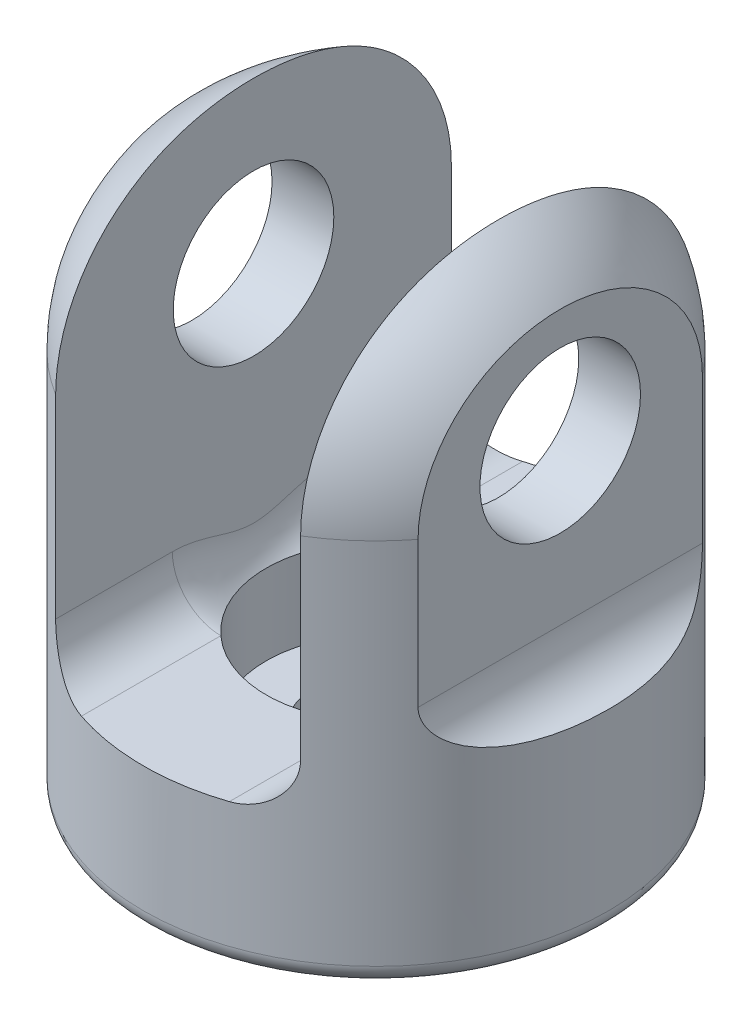
SolidWorks part; units mm, degrees
ref_plane "前视基准面" through (0, 0, 0) normal (0, 0, 1) x (1, 0, 0)
ref_plane "上视基准面" through (0, 0, 0) normal (0, 1, 0) x (1, 0, 0)
ref_plane "右视基准面" through (0, 0, 0) normal (1, 0, 0) x (0, 0, -1)
sketch "草图1" plane through (0, 0, 0) normal (0, 1, 0) x (1, 0, 0)
  circle A0 centre (0, 0) radius 12
  dimension "D1" = 24
extrude "凸台-拉伸1" add sketch "草图1" along normal blind 30 contours A0
fillet "圆角4" radius 10 1 edges at (0, 30, 12)
sketch "草图2" plane through (0, 0, 0) normal (0, 0, 1) x (1, 0, 0)
  line L0 (0, -13.2) -> (0, 13.2) construction
  line L1 (12, 30) -> (-12, 30) construction
  line L2 (-6.315, 30) -> (6.315, 30)
  line L3 (-6.315, 30) -> (-6.315, 7.47)
  line L4 (-6.315, 7.47) -> (6.315, 7.47)
  line L5 (6.315, 30) -> (6.315, 7.47)
  line L6 (-6.315, 30) -> (6.315, 7.47) construction
  line L7 (-6.315, 7.47) -> (6.315, 30) construction
  point P2 (0, 18.735)
  dimension "D1" = 12.63
  dimension "D2" = 22.53
sketch "草图5" plane through (0, 0, 0) normal (0, 1, 0) x (1, 0, 0)
  circle A0 centre (0, 0) radius 11
  dimension "D1" = 22
extrude "切除-拉伸4" cut sketch "草图5" along normal blind 1
sketch "草图7" plane through (0, 0, 0) normal (0, 1, 0) x (1, 0, 0)
  circle A0 centre (0, 0) radius 5.665
  dimension "D1" = 11.33
extrude "切除-拉伸6" cut sketch "草图7" along normal blind 10 from offset 3.33
sketch "草图6" plane through (0, 0, 0) normal (0, 1, 0) x (1, 0, 0)
  circle A0 centre (0, 0) radius 3.215
  dimension "D1" = 6.43
extrude "切除-拉伸5" cut sketch "草图6" along normal blind 4
fillet "圆角3" radius 1 1 edges at (0, 0, 12)
extrude "切除-拉伸2" cut sketch "草图2" against normal through all both and the other way through all
sketch "草图3" plane through (0, 0, 0) normal (0, 0, 1) x (1, 0, 0)
  line L0 (11, 0) -> (-11, 0) construction
  line L1 (9.5, 28) -> (12, 28)
  line L2 (9.5, 28) -> (9.5, 10)
  line L3 (9.5, 10) -> (12, 10)
  line L4 (12, 28) -> (12, 10)
  line L5 (12, 1) -> (12, 20) construction
  line L6 (0, -13.2) -> (0, 13.2) construction
  line L7 (-9.5, 10) -> (-12, 10)
  line L8 (-9.5, 28) -> (-12, 28)
  line L9 (-12, 28) -> (-12, 10)
  line L10 (-9.5, 28) -> (-9.5, 10)
  dimension "D1" = 18
  dimension "D2" = 2.5
  dimension "D3" = 10
extrude "切除-拉伸1" cut sketch "草图3" against normal through all both and the other way through all
sketch "草图4" plane through (0, 0, 0) normal (1, 0, 0) x (0, 0, -1)
  line L0 (0, 13.2) -> (0, -13.2) construction
  circle A0 centre (0, 20.75) radius 4.14
  dimension "D1" = 8.28
extrude "切除-拉伸3" cut sketch "草图4" against normal through all both and the other way through all contours A0
fillet "圆角2" radius 2.5 4 edges at (6.315, 7.47, 0) (-6.315, 7.47, 0) (-9.5, 10, 0) (9.5, 10, 0)
